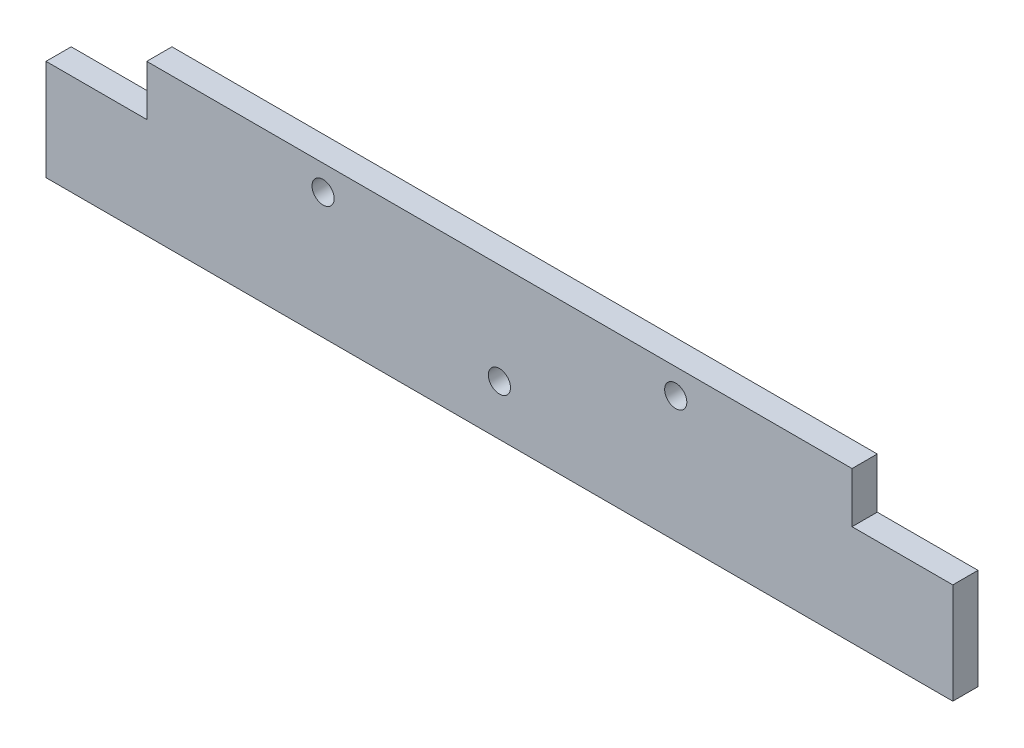
SolidWorks part; units mm, degrees
ref_plane "Płaszczyzna przednia" through (0, 0, 0) normal (0, 0, 1) x (1, 0, 0)
ref_plane "Płaszczyzna górna" through (0, 0, 0) normal (0, 1, 0) x (1, 0, 0)
ref_plane "Płaszczyzna prawa" through (0, 0, 0) normal (1, 0, 0) x (0, 0, -1)
sketch "Szkic1" plane through (0, 0, 0) normal (0, 0, 1) x (1, 0, 0)
  line L0 (0, -10) -> (-20, -10)
  line L2 (0, -10) -> (0, 0)
  line L3 (0, 0) -> (140, 0)
  line L4 (140, -10) -> (140, 0)
  line L7 (-20, -10) -> (-20, -30)
  line L8 (-20, -30) -> (160, -30)
  line L9 (160, -30) -> (160, -10)
  line L10 (160, -10) -> (140, -10)
  point P0 (0, 0)
  dimension "D1" = 180
  dimension "D2" = 30
  dimension "D3" = 10
  dimension "D4" = 20
  dimension "D5" = 20
extrude "Dodanie-wyciągnięcie1" add sketch "Szkic1" along normal blind 5
sketch "Szkic2" plane through (0, 0, 5) normal (0, 0, 1) x (1, 0, 0)
  line L0 (140, 0) -> (0, 0) construction
  line L1 (0, 0) -> (0, -10) construction
  line L2 (140, -10) -> (140, 0) construction
  circle A0 centre (35, -5) radius 2.2
  circle A2 centre (105, -5) radius 2.2
  dimension "D1" = 5
  dimension "D4" = 4.4
  dimension "D2" = 35
  dimension "D3" = 35
extrude "Wytnij-wyciągnięcie1" cut sketch "Szkic2" against normal blind 10
sketch "Szkic6" plane through (0, 0, 5) normal (0, 0, 1) x (1, 0, 0)
  line L0 (-20, -30) -> (160, -30) construction
  line L1 (160, -30) -> (160, -10) construction
  circle A0 centre (70, -20) radius 2.2
  dimension "D1" = 10
  dimension "D2" = 4.4
  dimension "D3" = 90
extrude "Wytnij-wyciągnięcie3" cut sketch "Szkic6" against normal through all
